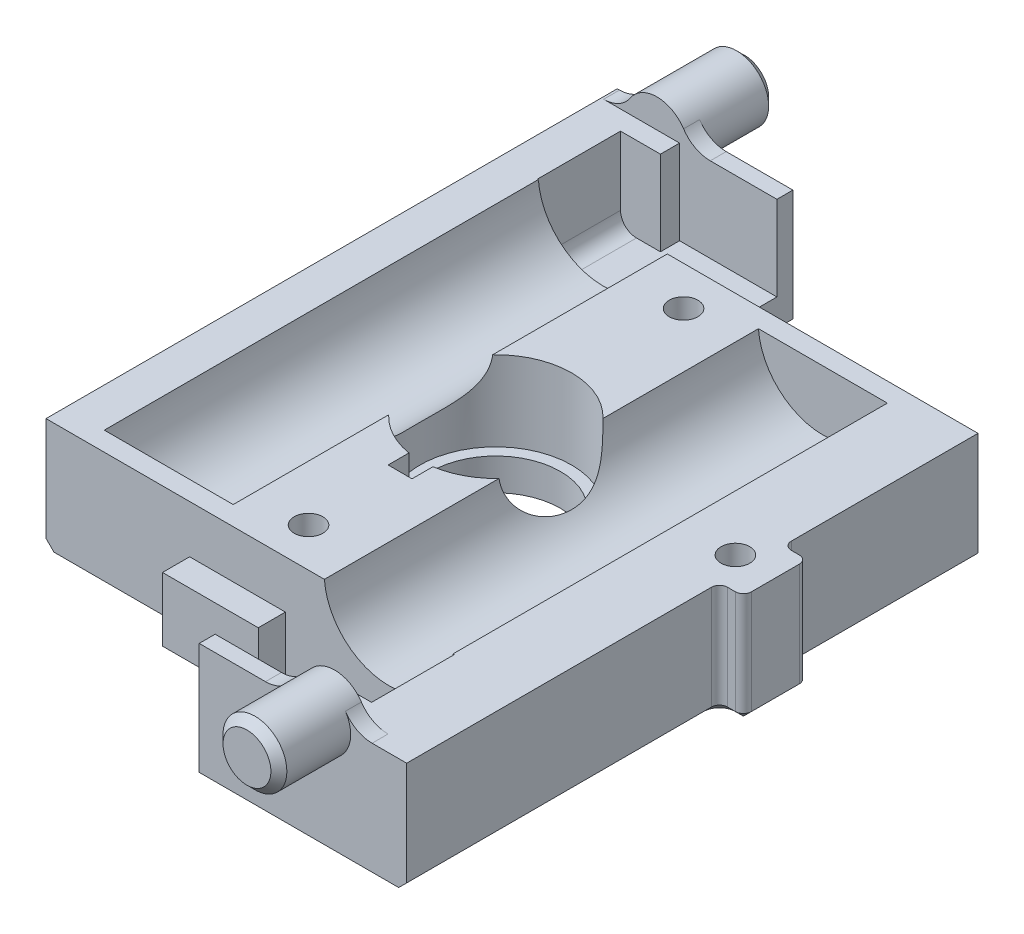
SolidWorks part; units mm, degrees
ref_plane "Front Plane" through (0, 0, 0) normal (0, 0, 1) x (1, 0, 0)
ref_plane "Top Plane" through (0, 0, 0) normal (0, 1, 0) x (1, 0, 0)
ref_plane "Right Plane" through (0, 0, 0) normal (1, 0, 0) x (0, 0, -1)
sketch "Sketch1" plane through (0, 0, 0) normal (0, 1, 0) x (1, 0, 0)
  line L1 (-61.4569, -66.3705) -> (-31.4569, -66.3705)
  line L2 (-61.4569, -66.3705) -> (-61.4569, -35.5705)
  line L3 (-61.4569, -35.5705) -> (-31.4569, -35.5705)
  line L4 (-31.4569, -66.3705) -> (-31.4569, -35.5705)
  dimension "D1" = 30.8
  dimension "D2" = 30
extrude "Boss-Extrude1" add sketch "Sketch1" along normal blind 7
sketch "Sketch2" plane through (0, 0, 0) normal (0, -1, 0) x (1, 0, 0)
  circle A0 centre (-47.4719, 50.9705) radius 4.05
  dimension "D1" = 8.1
extrude "Cut-Extrude1" cut sketch "Sketch2" against normal blind 6.5
sketch "Sketch3" plane through (0, 0, 0) normal (0, -1, 0) x (1, 0, 0)
  line L1 (-31.4569, 66.3705) -> (-46.4569, 66.3705)
  line L2 (-31.4569, 66.3705) -> (-31.4569, 65.1705)
  line L3 (-31.4569, 65.1705) -> (-46.4569, 65.1705)
  line L4 (-46.4569, 66.3705) -> (-46.4569, 65.1705)
  line L5 (-61.4569, 66.3705) -> (-52.4569, 66.3705)
  line L6 (-61.4569, 66.3705) -> (-61.4569, 65.1705)
  line L7 (-61.4569, 65.1705) -> (-52.4569, 65.1705)
  line L8 (-52.4569, 66.3705) -> (-52.4569, 65.1705)
  line L9 (-31.4569, 35.5705) -> (-42.4569, 35.5705)
  line L10 (-31.4569, 35.5705) -> (-31.4569, 36.7705)
  line L11 (-31.4569, 36.7705) -> (-42.4569, 36.7705)
  line L12 (-42.4569, 35.5705) -> (-42.4569, 36.7705)
  line L13 (-61.4569, 35.5705) -> (-48.4569, 35.5705)
  line L14 (-61.4569, 35.5705) -> (-61.4569, 36.7705)
  line L15 (-61.4569, 36.7705) -> (-48.4569, 36.7705)
  line L16 (-48.4569, 35.5705) -> (-48.4569, 36.7705)
  dimension "D1" = 15
  dimension "D2" = 9
  dimension "D3" = 1.2
  dimension "D4" = 1.2
  dimension "D5" = 1.2
  dimension "D6" = 1.2
  dimension "D7" = 11
  dimension "D8" = 13
extrude "Cut-Extrude2" cut sketch "Sketch3" against normal blind 4
sketch "Sketch4" plane through (0, 0, 66.3705) normal (0, 0, 1) x (1, 0, 0)
  line L1 (-61.4569, 7) -> (-31.4569, 7)
  line L2 (-61.4569, 7) -> (-61.4569, 4)
  line L3 (-61.4569, 4) -> (-31.4569, 4)
  line L4 (-31.4569, 7) -> (-31.4569, 4)
extrude "Cut-Extrude3" cut sketch "Sketch4" against normal blind 1.2
sketch "Sketch5" plane through (0, 0, 35.5705) normal (0, 0, -1) x (-1, 0, 0)
  line L1 (61.4569, 4) -> (31.4569, 4)
  line L2 (61.4569, 4) -> (61.4569, 7)
  line L3 (61.4569, 7) -> (31.4569, 7)
  line L4 (31.4569, 4) -> (31.4569, 7)
extrude "Cut-Extrude4" cut sketch "Sketch5" against normal blind 1.2
sketch "Sketch6" plane through (0, 0, 65.1705) normal (0, 0, 1) x (1, 0, 0)
  line L0 (-44.0746, 7.3) -> (-35.8746, 7.3) construction
  circle A0 centre (-39.9746, 7.3) radius 4.05
  dimension "D1" = 8.1
extrude "Cut-Extrude5" cut sketch "Sketch6" against normal blind 27.2
sketch "Sketch7" plane through (0, 0, 36.7705) normal (0, 0, -1) x (-1, 0, 0)
  line L0 (50.8646, 7.3) -> (59.0646, 7.3) construction
  circle A0 centre (54.9646, 7.3) radius 4.05
  dimension "D1" = 8.1
extrude "Cut-Extrude6" cut sketch "Sketch7" against normal blind 27.2
sketch "Sketch8" plane through (0, 7, 0) normal (0, 1, 0) x (1, 0, 0)
  circle A0 centre (-47.4719, -50.9705) radius 4.75
  dimension "D1" = 9.5
extrude "Cut-Extrude7" cut sketch "Sketch8" against normal blind 5
sketch "Sketch10" plane through (0, 0, 65.1705) normal (0, 0, 1) x (1, 0, 0)
  line L5 (-31.4569, 0) -> (-31.4569, 7)
  line L6 (-31.4569, 7) -> (-35.8569, 7)
  line L7 (-31.4569, 7) -> (-35.9357, 7) construction
  line L8 (-35.8569, 7) -> (-35.8569, 1.7)
  line L9 (-35.8569, 1.7) -> (-44.4569, 1.7)
  line L10 (-44.4569, 1.7) -> (-44.4569, 0)
  line L11 (-46.4569, 0) -> (-31.4569, 0) construction
  line L12 (-44.4569, 0) -> (-31.4569, 0)
  dimension "D1" = 4.4
  dimension "D2" = 1.7
  dimension "D3" = 13
extrude "Boss-Extrude2" add sketch "Sketch10" along normal blind 6.4
fillet "Fillet1" radius 1 1 edges at (-35.8569, 1.7, 68.3705)
sketch "Sketch11" plane through (0, 0, 36.7705) normal (0, 0, -1) x (-1, 0, 0)
  line L0 (61.4569, 7) -> (61.4569, 0)
  line L1 (61.4569, 0) -> (50.4569, 0)
  line L2 (48.4569, 0) -> (61.4569, 0) construction
  line L3 (50.4569, 0) -> (50.4569, 1.7)
  line L4 (50.4569, 1.7) -> (59.0569, 1.7)
  line L5 (59.0569, 1.7) -> (59.0569, 7)
  line L6 (61.4569, 7) -> (59.0034, 7) construction
  line L7 (59.0569, 7) -> (61.4569, 7)
  dimension "D1" = 2.4
  dimension "D2" = 1.7
  dimension "D3" = 11
extrude "Boss-Extrude3" add sketch "Sketch11" along normal blind 6.4
fillet "Fillet2" radius 1 1 edges at (-59.0569, 1.7, 33.5705)
sketch "Sketch12" plane through (0, 7, 0) normal (0, 1, 0) x (1, 0, 0)
  line L1 (-46.7219, -56.9705) -> (-48.2219, -56.9705)
  line L2 (-46.7219, -56.9705) -> (-46.7219, -55.6264)
  line L3 (-46.7219, -55.6264) -> (-48.2219, -55.6264)
  line L4 (-48.2219, -56.9705) -> (-48.2219, -55.6264)
  arc A0 (-46.9719, -55.5935) -> (-47.9719, -55.5935) centre (-47.4719, -50.9705) ccw construction
  dimension "D1" = 1.5
  dimension "D2" = 0.75
  dimension "D3" = 6
extrude "Cut-Extrude8" cut sketch "Sketch12" against normal up to surface (5 mm away) up to face at (-47.4719, 2, 55.7205)
sketch "Sketch13" plane through (0, 0, 71.5705) normal (0, 0, 1) x (1, 0, 0)
  line L0 (-44.0134, 7) -> (-61.4569, 7) construction
  line L1 (-31.4569, 0) -> (-44.4569, 0)
  line L2 (-31.4569, 0) -> (-31.4569, 7)
  line L3 (-31.4569, 7) -> (-44.4569, 7)
  line L4 (-44.4569, 0) -> (-44.4569, 7)
extrude "Boss-Extrude4" add sketch "Sketch13" along normal blind 1
sketch "Sketch14" plane through (0, 0, 30.3705) normal (0, 0, -1) x (-1, 0, 0)
  line L0 (50.9257, 7) -> (31.4569, 7) construction
  line L1 (61.4569, 0) -> (50.4569, 0)
  line L2 (61.4569, 0) -> (61.4569, 7)
  line L3 (61.4569, 7) -> (50.4569, 7)
  line L4 (50.4569, 0) -> (50.4569, 7)
extrude "Boss-Extrude5" add sketch "Sketch14" along normal blind 1
sketch "Sketch15" plane through (0, 0, 71.5705) normal (0, 0, 1) x (1, 0, 0)
  circle A0 centre (-36.9646, 6.8) radius 2
  dimension "D1" = 4
sketch "Sketch16" plane through (0, 0, 30.3705) normal (0, 0, -1) x (-1, 0, 0)
  circle A0 centre (57.9746, 6.8) radius 2
  dimension "D1" = 4
extrude "Boss-Extrude8" add sketch "Sketch15" along normal blind 5.5
extrude "Boss-Extrude9" add sketch "Sketch16" along normal blind 5.5
fillet "Fillet3" radius 2 1 edges at (-59.9645, 7, 29.8705)
fillet "Fillet4" radius 2 1 edges at (-55.9846, 7, 29.8705)
fillet "Fillet5" radius 2 2 edges at (-34.9746, 7, 72.0705) (-38.9545, 7, 72.0705)
chamfer "Chamfer2" distance 0.5 angle 45 1 edges at (-34.9646, 6.8, 77.0705)
chamfer "Chamfer3" distance 0.5 angle 45 1 edges at (-59.9746, 6.8, 24.8705)
sketch "Sketch17" plane through (-31.4569, 0, 0) normal (1, 0, 0) x (0, 0, -1)
  line L0 (-72.5705, 7) -> (-36.7705, 7) construction
  line L1 (-52.9705, 7) -> (-48.9705, 7)
  line L2 (-52.9705, 7) -> (-52.9705, 0)
  line L3 (-52.9705, 0) -> (-48.9705, 0)
  line L4 (-48.9705, 7) -> (-48.9705, 0)
  line L5 (-72.5705, 0) -> (-36.7705, 0) construction
  line L6 (-36.7705, 7) -> (-36.7705, 0) construction
  dimension "D1" = 4
  dimension "D2" = 12.2
extrude "Boss-Extrude10" add sketch "Sketch17" along normal blind 1.5
fillet "Fillet7" radius 0.5 4 edges at (-31.4569, 3.5, 52.9705) (-29.9569, 3.5, 52.9705) (-29.9569, 3.5, 48.9705) (-31.4569, 3.5, 48.9705)
sketch "Sketch18" plane through (0, 0, 0) normal (0, -1, 0) x (1, 0, 0)
  circle A0 centre (-32.4569, 50.9705) radius 0.9
  dimension "D1" = 1.8
extrude "Cut-Extrude9" cut sketch "Sketch18" against normal through all
sketch "Sketch19" plane through (0, 0, 0) normal (0, -1, 0) x (1, 0, 0)
  circle A0 centre (-32.4569, 50.9705) radius 1.6
  dimension "D1" = 3.2
extrude "Cut-Extrude10" cut sketch "Sketch19" against normal blind 2
sketch "Sketch20" plane through (0, 0, 0) normal (0, -1, 0) x (1, 0, 0)
  circle A0 centre (-47.4569, 62.7205) radius 0.9
  circle A1 centre (-47.4569, 39.2205) radius 0.9
  dimension "D1" = 1.8
  dimension "D2" = 1.8
extrude "Cut-Extrude11" cut sketch "Sketch20" against normal through all
sketch "Sketch21" plane through (0, 0, 0) normal (0, -1, 0) x (1, 0, 0)
  circle A0 centre (-47.4569, 62.7205) radius 1.6
  circle A1 centre (-47.4569, 39.2205) radius 1.6
  dimension "D1" = 3.2
  dimension "D2" = 3.2
extrude "Cut-Extrude12" cut sketch "Sketch21" against normal blind 2
chamfer "Chamfer6" distance 0.5 angle 45 10 edges at (-61.4569, 0, 47.2705) (-31.4569, 0, 42.6205) (-31.3104, 0, 48.8241) (-30.7069, 0, 48.9705) (-30.1033, 0, 49.117) (-29.9569, 0, 50.9705) (-30.1033, 0, 52.8241) (-30.7069, 0, 52.9705) (-31.3104, 0, 53.117) (-31.4569, 0, 63.0205)
sketch "Sketch22" plane through (0, 0, 35.5705) normal (0, 0, -1) x (-1, 0, 0)
  line L1 (42.4569, 4) -> (48.4569, 4)
  line L2 (42.4569, 4) -> (42.4569, 0)
  line L3 (42.4569, 0) -> (48.4569, 0)
  line L4 (48.4569, 4) -> (48.4569, 0)
extrude "Boss-Extrude11" add sketch "Sketch22" along normal blind 0.5
sketch "Sketch23" plane through (0, 0, 66.3705) normal (0, 0, 1) x (1, 0, 0)
  line L1 (-52.4569, 4) -> (-46.4569, 4)
  line L2 (-52.4569, 4) -> (-52.4569, 0)
  line L3 (-52.4569, 0) -> (-46.4569, 0)
  line L4 (-46.4569, 4) -> (-46.4569, 0)
extrude "Boss-Extrude12" add sketch "Sketch23" along normal blind 0.5
sketch "Sketch24" plane through (0, 7, 0) normal (0, 1, 0) x (1, 0, 0)
  line L0 (-35.8569, -65.1705) -> (-35.8569, -71.5705) construction
  line L1 (-33.6239, -71.5705) -> (-38.3569, -71.5705)
  line L2 (-33.6239, -71.5705) -> (-33.6239, -70.3705)
  line L3 (-33.6239, -70.3705) -> (-38.3569, -70.3705)
  line L4 (-38.3569, -71.5705) -> (-38.3569, -70.3705)
  line L5 (-59.0569, -36.7705) -> (-59.0569, -30.3705) construction
  line L6 (-61.3152, -30.3705) -> (-56.5569, -30.3705)
  line L7 (-61.3152, -30.3705) -> (-61.3152, -31.5705)
  line L8 (-61.3152, -31.5705) -> (-56.5569, -31.5705)
  line L9 (-56.5569, -30.3705) -> (-56.5569, -31.5705)
  dimension "D1" = 1.2
  dimension "D2" = 2.5
  dimension "D3" = 1.2
  dimension "D4" = 2.5
extrude "Boss-Extrude13" add sketch "Sketch24" against normal up to surface (5.3 mm away) up to face at (-54.2569, 1.7, 33.5705)
